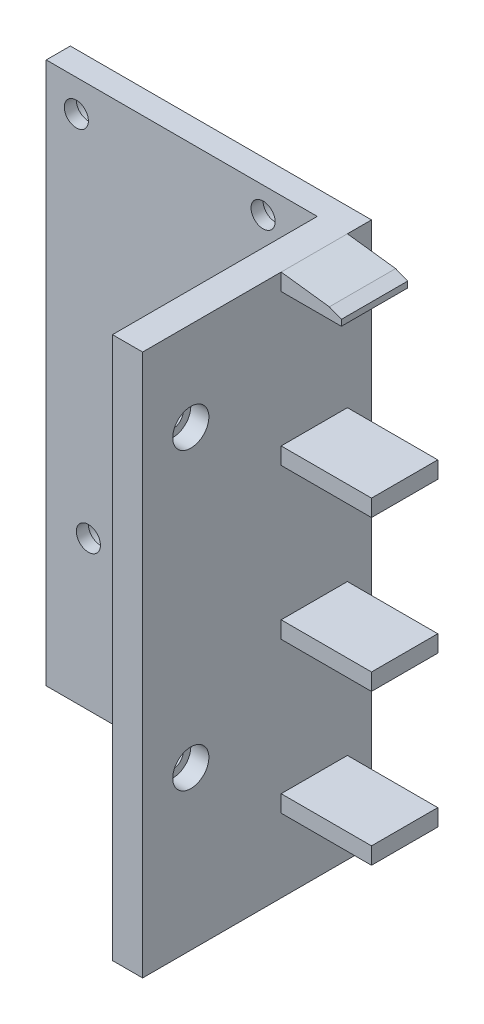
SolidWorks part; units mm, degrees
note: The reader was unsure of these and kept them because the rebuilt part matched: shared geometry of "스케치1<3>", "스케치1<4>", "스케치11<3>", "스케치15<3>", "스케치17<2>", "스케치17<4>".
ref_plane "정면" through (0, 0, 0) normal (0, 0, 1) x (1, 0, 0)
ref_plane "윗면" through (0, 0, 0) normal (0, 1, 0) x (1, 0, 0)
ref_plane "우측면" through (0, 0, 0) normal (1, 0, 0) x (0, 0, -1)
sketch "스케치1" plane through (0, 0, 0) normal (0, 0, 1) x (1, 0, 0)
  line L0 (15, -3) -> (15, -3.8)
  line L1 (0, 0) -> (5, 0)
  line L2 (0, 0) -> (0, -77.8)
  line L3 (0, -77.8) -> (5, -77.8)
  line L4 (5, 0) -> (5, -77.8)
  line L6 (5, 0) -> (5, -0.7461)
  line L8 (15, -1.8) -> (15, -3)
  line L9 (5, -25) -> (20, -25)
  line L10 (5, -25) -> (5, -27.8)
  line L11 (5, -27.8) -> (20, -27.8)
  line L12 (20, -25) -> (20, -27.8)
  line L13 (5, -50) -> (20, -50)
  line L14 (5, -50) -> (5, -52.8)
  line L15 (5, -52.8) -> (20, -52.8)
  line L16 (20, -50) -> (20, -52.8)
  line L17 (5, -75) -> (20, -75)
  line L18 (5, -75) -> (5, -77.8)
  line L19 (5, -77.8) -> (20, -77.8)
  line L20 (20, -75) -> (20, -77.8)
  line L21 (15, -3.8) -> (13, -3.8)
  line L22 (13, -3.8) -> (13, -1)
  line L23 (15, -3.8) -> (15, -3)
  line L24 (13, -2.8) -> (5, -2.8)
  line L25 (5, 0) -> (13, -1)
  line L26 (13, -1) -> (15, -1.8)
  line L28 (0, -77.8) -> (5, -77.8)
  line L29 (0, -77.8) -> (0, -80)
  line L30 (0, -80) -> (5, -80)
  line L31 (5, -77.8) -> (5, -80)
  dimension "D15" = 1
  dimension "D1" = 5
  dimension "D2" = 80
  dimension "D3" = 2.8
  dimension "D4" = 2.8
  dimension "D5" = 2.8
  dimension "D6" = 2.8
  dimension "D7" = 2.8
  dimension "D8" = 25
  dimension "D9" = 25
  dimension "D10" = 10
  dimension "D11" = 15
  dimension "D12" = 15
  dimension "D13" = 15
  dimension "D14" = 2
  dimension "D16" = 2
  dimension "D17" = 25
extrude "보스-돌출1" add sketch "스케치1" along normal blind 38
extrude "보스-돌출7" add sketch "스케치1<3>" along normal blind 38 contours L25 L4 L24 L22
sketch "스케치1<3>" plane through (0, 0, 0) normal (0, 0, 1) x (1, 0, 0) same geometry as "스케치1"
sketch "스케치11" plane through (0, 0, 0) normal (-1, 0, 0) x (0, 0, 1)
  line L0 (38, 0) -> (38, -77.8) construction
  circle A0 centre (30, -63.7698) radius 1.75
  circle A1 centre (30, -14.8193) radius 1.75
  circle A2 centre (30, -63.7698) radius 3
  circle A3 centre (30, -14.8193) radius 3
  dimension "D1" = 3.5
  dimension "D2" = 3.5
  dimension "D3" = 6
  dimension "D4" = 6
  dimension "D5" = 8
  dimension "D6" = 8
sketch "스케치13" plane through (0, 0, 0) normal (0, 1, 0) x (1, 0, 0)
  line L1 (0, 0) -> (-45, 0)
  line L2 (0, 0) -> (0, -4)
  line L3 (0, -4) -> (-45, -4)
  line L4 (-45, 0) -> (-45, -4)
  dimension "D1" = 45
  dimension "D2" = 4
extrude "보스-돌출9" add sketch "스케치13" against normal blind 90 contours L1 L4 L3 L2
extrude "보스-돌출10" add sketch "스케치1<4>" along normal blind 38 contours L29 L30 L31 L28
sketch "스케치1<4>" plane through (0, 0, 0) normal (0, 0, 1) x (1, 0, 0) same geometry as "스케치1"
extrude "컷-돌출2" cut sketch "스케치11" against normal blind 38 contours A0 | A1
extrude "컷-돌출3" cut sketch "스케치11<3>" against normal blind 38 from offset 2 offset against normal yes
sketch "스케치11<3>" plane through (0, 0, 0) normal (-1, 0, 0) x (0, 0, 1) same geometry as "스케치11"
sketch "스케치15" plane through (0, 0, 4) normal (0, 0, 1) x (1, 0, 0)
  line L0 (-45, -90) -> (-45, 0) construction
  circle A0 centre (-40, -5.2842) radius 2
  circle A1 centre (-9, -4.2842) radius 2
  circle A2 centre (-9, -65.2842) radius 2
  circle A3 centre (-38, -65.2842) radius 2
  circle A4 centre (-40, -5.2842) radius 3
  circle A5 centre (-38, -65.2842) radius 3
  circle A6 centre (-9, -65.2842) radius 3
  circle A7 centre (-9, -4.2842) radius 3
  dimension "D1" = 4
  dimension "D2" = 4
  dimension "D3" = 4
  dimension "D4" = 4
  dimension "D10" = 6
  dimension "D11" = 6
  dimension "D12" = 6
  dimension "D13" = 6
  dimension "D5" = 61
  dimension "D6" = 31
  dimension "D7" = 29
  dimension "D8" = 60
  dimension "D9" = 5
extrude "컷-돌출4" cut sketch "스케치15" against normal blind 38 contours A0 | A1 | A2 | A3
extrude "컷-돌출5" cut sketch "스케치15<3>" against normal blind 38 from offset 2 offset against normal yes
sketch "스케치15<3>" plane through (0, 0, 4) normal (0, 0, 1) x (1, 0, 0) same geometry as "스케치15"
sketch "스케치17" plane through (0, 0, 38) normal (0, 0, 1) x (1, 0, 0)
  line L1 (0, -80) -> (5, -80)
  line L2 (0, -80) -> (0, -90)
  line L3 (0, -90) -> (5, -90)
  line L4 (5, -80) -> (5, -90)
  line L5 (0, -90) -> (-45, -90) construction
  line L6 (5, -77.8) -> (5, -80) construction
  line L7 (5, -25) -> (20, -25)
  line L8 (5, -25) -> (5, -27.8)
  line L9 (5, -27.8) -> (20, -27.8)
  line L10 (20, -25) -> (20, -27.8)
  line L11 (5, -50) -> (20, -50)
  line L12 (5, -50) -> (5, -52.8)
  line L13 (5, -52.8) -> (20, -52.8)
  line L14 (20, -50) -> (20, -52.8)
  line L15 (5, -75) -> (20, -75)
  line L16 (5, -75) -> (5, -77.8)
  line L17 (5, -77.8) -> (20, -77.8)
  line L18 (20, -75) -> (20, -77.8)
  line L19 (15, -3.8) -> (5, -3.8)
  line L20 (15, -3.8) -> (15, 0)
  line L21 (15, 0) -> (5, 0)
  line L22 (5, -3.8) -> (5, 0)
  line M14 (5, -77.8) -> (20, -77.8)
  line M15 (20, -77.8) -> (20, -75)
  line M16 (20, -75) -> (5, -75)
extrude "보스-돌출12" add sketch "스케치17" against normal blind 23 contours L17 L18 L15 L16 | L13 L14 L11 L12 | L9 L10 L7 L8
sketch "스케치18" plane through (0, 0, 38) normal (0, 0, 1) x (1, 0, 0)
  line L0 (15, -1.8) -> (15, -3.8) construction
  line L1 (13, -3.8) -> (15, -3.8)
  line L2 (13, -3.8) -> (13, -2.8)
  line L3 (13, -2.8) -> (15, -2.8)
  line L4 (15, -3.8) -> (15, -2.8)
extrude "컷-돌출6" cut sketch "스케치18" against normal blind 40 contours L3 L4 L1 L2
ref_plane "평면1" through (20, -50, 38) normal (1, 0, 0) x (0, 0, -1)
extrude "컷-돌출7" cut sketch "스케치17<2>" against normal blind 23 contours L16 M16 M14 M15 | L11 L14 L13 L12 | L7 L10 L9 L8 | L19 L22 L21 L20
sketch "스케치17<2>" plane through (0, 0, 38) normal (0, 0, 1) x (1, 0, 0) same geometry as "스케치17"
sketch "스케치20" plane through (0, 0, 0) normal (0, 1, 0) x (1, 0, 0)
  line L0 (20, -93) -> (20, 17) construction
  line L1 (5, 0) -> (20, 0)
  line L2 (5, 0) -> (5, -4)
  line L3 (5, -4) -> (20, -4)
  line L4 (20, 0) -> (20, -4)
  line L5 (0, -4) -> (-45, -4) construction
extrude "컷-돌출8" cut sketch "스케치20" against normal blind 89
ref_plane "평면2" through (0, -80, 38) normal (1, 0, 0) x (0, 0, -1)
extrude "보스-돌출13" add sketch "스케치17<4>" against normal up to vertex (38 mm away) contours L4 L3 L2 L1
sketch "스케치17<4>" plane through (0, 0, 38) normal (0, 0, 1) x (1, 0, 0) same geometry as "스케치17"
